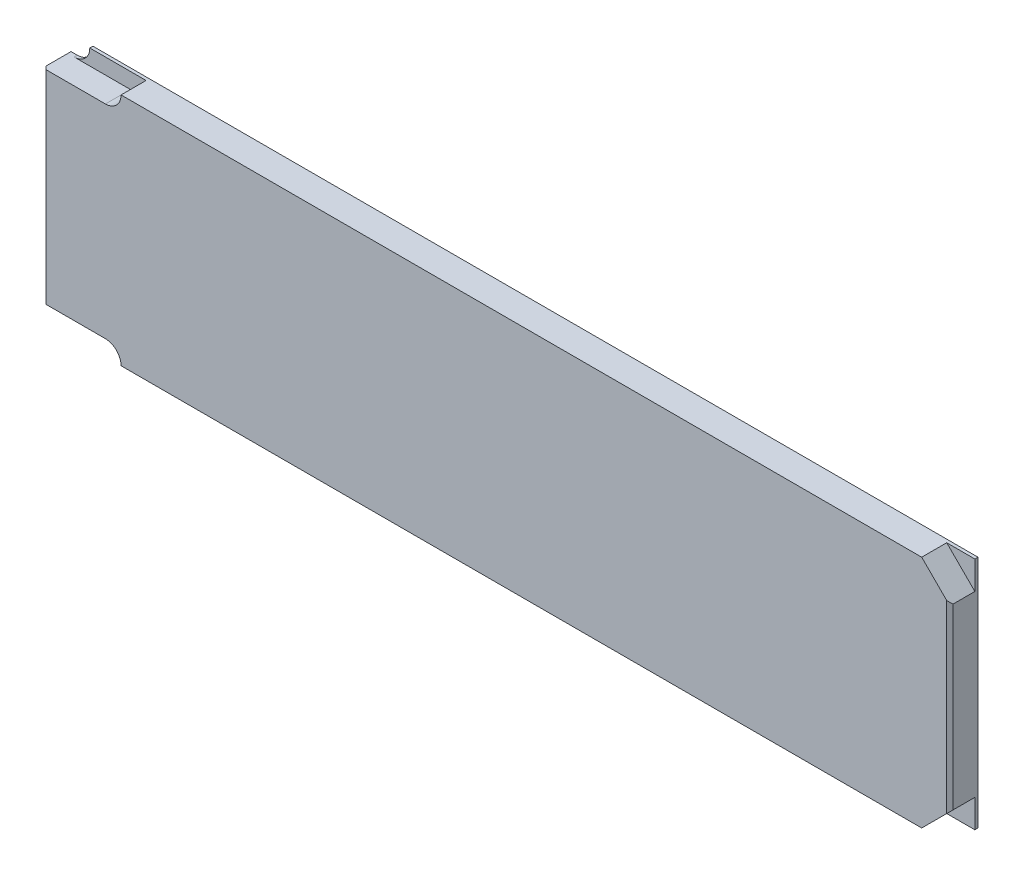
SolidWorks part; units mm, degrees
ref_plane "Plane1" through (0, 0, 0) normal (0, 0, 1) x (1, 0, 0)
ref_plane "Plane2" through (0, 0, 0) normal (0, 1, 0) x (1, 0, 0)
ref_plane "Plane3" through (0, 0, 0) normal (1, 0, 0) x (0, 0, -1)
sketch "Sketch1" plane through (0, 0, 0) normal (0, 0, 1) x (1, 0, 0)
  line L0 (7, 0) -> (7, 5)
  line L1 (7, 0) -> (290, 0)
  line L2 (0, 5) -> (0, 70)
  line L3 (7, 75) -> (290, 75)
  line L4 (290, 0) -> (290, 75)
  line L5 (7, 5) -> (0, 5)
  line L6 (0, 70) -> (7, 70)
  line L7 (7, 70) -> (7, 75)
  dimension "D1" = 75
  dimension "D2" = 290
  dimension "D3" = 7
  dimension "D4" = 5
extrude "Base-Extrude" add sketch "Sketch1" along normal blind 9
sketch "Sketch2" plane through (0, 0, 9) normal (0, 0, 1) x (1, 0, 0)
  line L0 (281, 75) -> (290, 66)
  line L1 (290, 75) -> (7, 75) construction
  line L2 (290, 0) -> (290, 75) construction
  line L3 (290, 9) -> (281, 0)
  line L4 (7, 0) -> (290, 0) construction
  line L5 (25, 75) -> (25, 70)
  line L6 (0, 5) -> (7, 5) construction
  line L7 (7, 70) -> (0, 70) construction
  line L8 (290, 75) -> (281, 75)
  line L9 (290, 0) -> (290, 9)
  line L10 (0, 0) -> (25, 0)
  line L11 (0, 5) -> (25, 5)
  line L12 (25, 70) -> (0, 70)
  line L13 (0, 70) -> (0, 5) construction
  line L14 (0, 75) -> (0, 70)
  line L17 (25, 5) -> (25, 0)
  line L18 (0, 5) -> (0, 0)
  line L19 (25, 75) -> (0, 75)
  line L20 (290, 66) -> (290, 75)
  line L21 (281, 0) -> (290, 0)
  dimension "D1" = 25
  dimension "D2" = 9
  dimension "D3" = 9
extrude "Cut-Extrude1" cut sketch "Sketch2" against normal blind 8
chamfer "Chamfer1" distance 1 angle 45 2 edges at (0, 37.5, 9) (290, 37.5, 9)
fillet "Fillet1" radius 5 4 edges at (25, 70, 5) (7, 70, 0.5) (25, 5, 5) (7, 5, 0.5)
